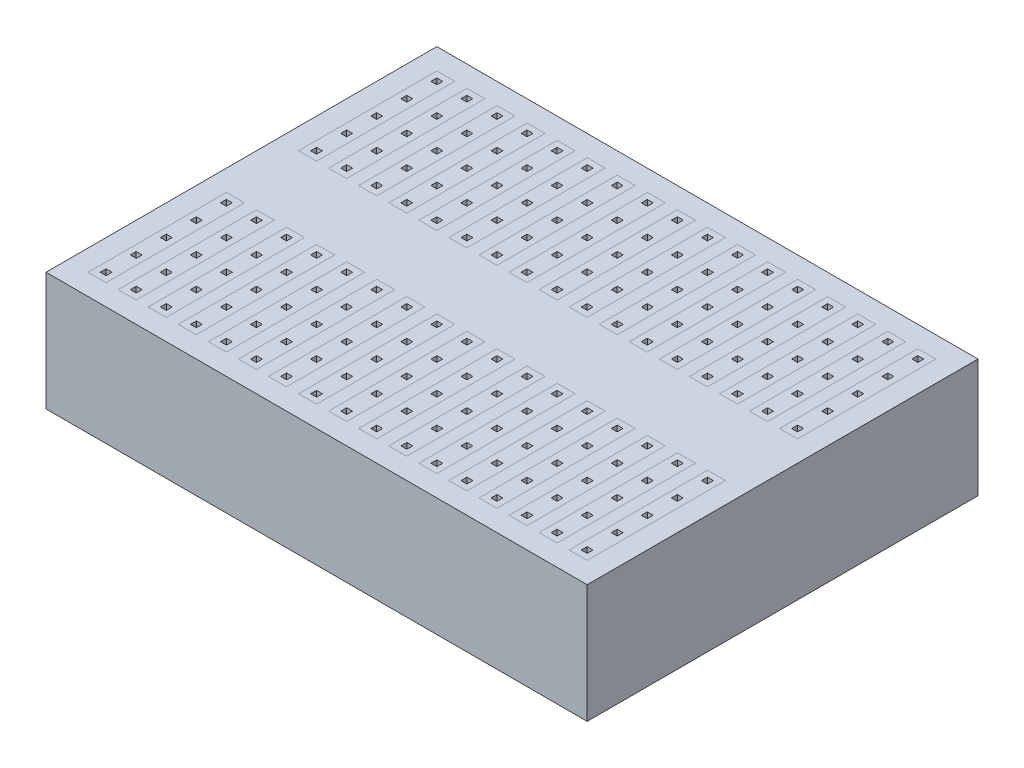
SolidWorks part; units mm, degrees
ref_plane "Front Plane" through (0, 0, 0) normal (0, 0, 1) x (1, 0, 0)
ref_plane "Top Plane" through (0, 0, 0) normal (0, 1, 0) x (1, 0, 0)
ref_plane "Right Plane" through (0, 0, 0) normal (1, 0, 0) x (0, 0, -1)
sketch "Sketch: Protoboard Body" plane through (0, 0, 0) normal (0, 1, 0) x (1, 0, 0)
  line L1 (-22.86, -16.51) -> (22.86, -16.51)
  line L2 (-22.86, -16.51) -> (-22.86, 16.51)
  line L3 (-22.86, 16.51) -> (22.86, 16.51)
  line L4 (22.86, -16.51) -> (22.86, 16.51)
  line L5 (-22.86, -16.51) -> (22.86, 16.51) construction
  line L6 (-22.86, 16.51) -> (22.86, -16.51) construction
  point P0 (0, 0)
extrude "Protoboard Body" add sketch "Sketch: Protoboard Body" against normal blind 10
sketch "Sketch: Terminal Strips" plane through (0, 0, 0) normal (0, 1, 0) x (1, 0, 0)
  line L0 (-18.54, -14.73) -> (-17.02, -14.73)
  line L1 (-21.08, -14.73) -> (-19.56, -14.73)
  line L2 (-21.08, -14.73) -> (-21.08, -3.05)
  line L3 (-21.08, -3.05) -> (-19.56, -3.05)
  line L4 (-19.56, -14.73) -> (-19.56, -3.05)
  line L9 (-18.54, -14.73) -> (-18.54, -3.05)
  line L10 (-18.54, -3.05) -> (-17.02, -3.05)
  line L11 (-17.02, -14.73) -> (-17.02, -3.05)
  line L12 (-16, -14.73) -> (-14.48, -14.73)
  line L13 (-16, -14.73) -> (-16, -3.05)
  line L14 (-16, -3.05) -> (-14.48, -3.05)
  line L15 (-14.48, -14.73) -> (-14.48, -3.05)
  line L16 (-13.46, -14.73) -> (-11.94, -14.73)
  line L17 (-13.46, -14.73) -> (-13.46, -3.05)
  line L18 (-13.46, -3.05) -> (-11.94, -3.05)
  line L19 (-11.94, -14.73) -> (-11.94, -3.05)
  line L20 (-10.92, -14.73) -> (-9.4, -14.73)
  line L21 (-10.92, -14.73) -> (-10.92, -3.05)
  line L22 (-10.92, -3.05) -> (-9.4, -3.05)
  line L23 (-9.4, -14.73) -> (-9.4, -3.05)
  line L24 (-8.38, -14.73) -> (-6.86, -14.73)
  line L25 (-8.38, -14.73) -> (-8.38, -3.05)
  line L26 (-8.38, -3.05) -> (-6.86, -3.05)
  line L27 (-6.86, -14.73) -> (-6.86, -3.05)
  line L28 (-5.84, -14.73) -> (-4.32, -14.73)
  line L29 (-5.84, -14.73) -> (-5.84, -3.05)
  line L30 (-5.84, -3.05) -> (-4.32, -3.05)
  line L31 (-4.32, -14.73) -> (-4.32, -3.05)
  line L32 (-3.3, -14.73) -> (-1.78, -14.73)
  line L33 (-3.3, -14.73) -> (-3.3, -3.05)
  line L34 (-3.3, -3.05) -> (-1.78, -3.05)
  line L35 (-1.78, -14.73) -> (-1.78, -3.05)
  line L36 (-0.76, -14.73) -> (0.76, -14.73)
  line L37 (-0.76, -14.73) -> (-0.76, -3.05)
  line L38 (-0.76, -3.05) -> (0.76, -3.05)
  line L39 (0.76, -14.73) -> (0.76, -3.05)
  line L40 (1.78, -14.73) -> (3.3, -14.73)
  line L41 (1.78, -14.73) -> (1.78, -3.05)
  line L42 (1.78, -3.05) -> (3.3, -3.05)
  line L43 (3.3, -14.73) -> (3.3, -3.05)
  line L44 (4.32, -14.73) -> (5.84, -14.73)
  line L45 (4.32, -14.73) -> (4.32, -3.05)
  line L46 (4.32, -3.05) -> (5.84, -3.05)
  line L47 (5.84, -14.73) -> (5.84, -3.05)
  line L48 (6.86, -14.73) -> (8.38, -14.73)
  line L49 (6.86, -14.73) -> (6.86, -3.05)
  line L50 (6.86, -3.05) -> (8.38, -3.05)
  line L51 (8.38, -14.73) -> (8.38, -3.05)
  line L52 (9.4, -14.73) -> (10.92, -14.73)
  line L53 (9.4, -14.73) -> (9.4, -3.05)
  line L54 (9.4, -3.05) -> (10.92, -3.05)
  line L55 (10.92, -14.73) -> (10.92, -3.05)
  line L56 (11.94, -14.73) -> (13.46, -14.73)
  line L57 (11.94, -14.73) -> (11.94, -3.05)
  line L58 (11.94, -3.05) -> (13.46, -3.05)
  line L59 (13.46, -14.73) -> (13.46, -3.05)
  line L60 (14.48, -14.73) -> (16, -14.73)
  line L61 (14.48, -14.73) -> (14.48, -3.05)
  line L62 (14.48, -3.05) -> (16, -3.05)
  line L63 (16, -14.73) -> (16, -3.05)
  line L64 (17.02, -14.73) -> (18.54, -14.73)
  line L65 (17.02, -14.73) -> (17.02, -3.05)
  line L66 (17.02, -3.05) -> (18.54, -3.05)
  line L67 (18.54, -14.73) -> (18.54, -3.05)
  line L68 (19.56, -14.73) -> (21.08, -14.73)
  line L69 (19.56, -14.73) -> (19.56, -3.05)
  line L70 (19.56, -3.05) -> (21.08, -3.05)
  line L71 (21.08, -14.73) -> (21.08, -3.05)
  line L72 (-18.54, 3.05) -> (-17.02, 3.05)
  line L73 (-18.54, 3.05) -> (-18.54, 14.73)
  line L74 (-18.54, 14.73) -> (-17.02, 14.73)
  line L75 (-17.02, 3.05) -> (-17.02, 14.73)
  line L76 (-16, 3.05) -> (-14.48, 3.05)
  line L77 (-16, 3.05) -> (-16, 14.73)
  line L78 (-16, 14.73) -> (-14.48, 14.73)
  line L79 (-14.48, 3.05) -> (-14.48, 14.73)
  line L80 (-13.46, 3.05) -> (-11.94, 3.05)
  line L81 (-13.46, 3.05) -> (-13.46, 14.73)
  line L82 (-13.46, 14.73) -> (-11.94, 14.73)
  line L83 (-11.94, 3.05) -> (-11.94, 14.73)
  line L84 (-10.92, 3.05) -> (-9.4, 3.05)
  line L85 (-10.92, 3.05) -> (-10.92, 14.73)
  line L86 (-10.92, 14.73) -> (-9.4, 14.73)
  line L87 (-9.4, 3.05) -> (-9.4, 14.73)
  line L88 (-8.38, 3.05) -> (-6.86, 3.05)
  line L89 (-8.38, 3.05) -> (-8.38, 14.73)
  line L90 (-8.38, 14.73) -> (-6.86, 14.73)
  line L91 (-6.86, 3.05) -> (-6.86, 14.73)
  line L92 (-5.84, 3.05) -> (-4.32, 3.05)
  line L93 (-5.84, 3.05) -> (-5.84, 14.73)
  line L94 (-5.84, 14.73) -> (-4.32, 14.73)
  line L95 (-4.32, 3.05) -> (-4.32, 14.73)
  line L96 (-3.3, 3.05) -> (-1.78, 3.05)
  line L97 (-3.3, 3.05) -> (-3.3, 14.73)
  line L98 (-3.3, 14.73) -> (-1.78, 14.73)
  line L99 (-1.78, 3.05) -> (-1.78, 14.73)
  line L100 (-0.76, 3.05) -> (0.76, 3.05)
  line L101 (-0.76, 3.05) -> (-0.76, 14.73)
  line L102 (-0.76, 14.73) -> (0.76, 14.73)
  line L103 (0.76, 3.05) -> (0.76, 14.73)
  line L104 (1.78, 3.05) -> (3.3, 3.05)
  line L105 (1.78, 3.05) -> (1.78, 14.73)
  line L106 (1.78, 14.73) -> (3.3, 14.73)
  line L107 (3.3, 3.05) -> (3.3, 14.73)
  line L108 (4.32, 3.05) -> (5.84, 3.05)
  line L109 (4.32, 3.05) -> (4.32, 14.73)
  line L110 (4.32, 14.73) -> (5.84, 14.73)
  line L111 (5.84, 3.05) -> (5.84, 14.73)
  line L112 (6.86, 3.05) -> (8.38, 3.05)
  line L113 (6.86, 3.05) -> (6.86, 14.73)
  line L114 (6.86, 14.73) -> (8.38, 14.73)
  line L115 (8.38, 3.05) -> (8.38, 14.73)
  line L116 (9.4, 3.05) -> (10.92, 3.05)
  line L117 (9.4, 3.05) -> (9.4, 14.73)
  line L118 (9.4, 14.73) -> (10.92, 14.73)
  line L119 (10.92, 3.05) -> (10.92, 14.73)
  line L120 (11.94, 3.05) -> (13.46, 3.05)
  line L121 (11.94, 3.05) -> (11.94, 14.73)
  line L122 (11.94, 14.73) -> (13.46, 14.73)
  line L123 (13.46, 3.05) -> (13.46, 14.73)
  line L124 (14.48, 3.05) -> (16, 3.05)
  line L125 (14.48, 3.05) -> (14.48, 14.73)
  line L126 (14.48, 14.73) -> (16, 14.73)
  line L127 (16, 3.05) -> (16, 14.73)
  line L128 (17.02, 3.05) -> (18.54, 3.05)
  line L129 (17.02, 3.05) -> (17.02, 14.73)
  line L130 (17.02, 14.73) -> (18.54, 14.73)
  line L131 (18.54, 3.05) -> (18.54, 14.73)
  line L132 (19.56, 3.05) -> (21.08, 3.05)
  line L133 (19.56, 3.05) -> (19.56, 14.73)
  line L134 (19.56, 14.73) -> (21.08, 14.73)
  line L135 (21.08, 3.05) -> (21.08, 14.73)
  line L136 (-21.08, 3.05) -> (-19.56, 3.05)
  line L137 (-21.08, 3.05) -> (-21.08, 14.73)
  line L138 (-21.08, 14.73) -> (-19.56, 14.73)
  line L139 (-19.56, 3.05) -> (-19.56, 14.73)
extrude "Space for Terminal Strips" cut sketch "Sketch: Terminal Strips" against normal blind 8.4
extrude "Terminal Strips" add sketch "Sketch3<2>" against normal blind 8.4 separate body
sketch "Sketch3<2>" plane through (0, 0, 0) normal (0, 1, 0) x (1, 0, 0) same geometry as "Sketch: Terminal Strips"
sketch "Sketch: Pin Holes" plane through (0, 0, 0) normal (0, 1, 0) x (1, 0, 0)
  line L1 (-20.57, -14.22) -> (-20.07, -14.22)
  line L2 (-20.57, -14.22) -> (-20.57, -13.72)
  line L3 (-20.57, -13.72) -> (-20.07, -13.72)
  line L4 (-20.07, -14.22) -> (-20.07, -13.72)
  line L5 (-20.57, -14.22) -> (-20.07, -13.72) construction
  line L6 (-20.57, -13.72) -> (-20.07, -14.22) construction
  line L8 (-20.57, -11.68) -> (-20.07, -11.68)
  line L9 (-20.57, -11.68) -> (-20.57, -11.18)
  line L10 (-20.57, -11.18) -> (-20.07, -11.18)
  line L11 (-20.07, -11.68) -> (-20.07, -11.18)
  line L12 (-20.57, -11.68) -> (-20.07, -11.18) construction
  line L13 (-20.57, -11.18) -> (-20.07, -11.68) construction
  line L14 (-20.57, -9.14) -> (-20.07, -9.14)
  line L15 (-20.57, -9.14) -> (-20.57, -8.64)
  line L16 (-20.57, -8.64) -> (-20.07, -8.64)
  line L17 (-20.07, -9.14) -> (-20.07, -8.64)
  line L18 (-20.57, -9.14) -> (-20.07, -8.64) construction
  line L19 (-20.57, -8.64) -> (-20.07, -9.14) construction
  line L20 (-20.57, -6.6) -> (-20.07, -6.6)
  line L21 (-20.57, -6.6) -> (-20.57, -6.1)
  line L22 (-20.57, -6.1) -> (-20.07, -6.1)
  line L23 (-20.07, -6.6) -> (-20.07, -6.1)
  line L24 (-20.57, -6.6) -> (-20.07, -6.1) construction
  line L25 (-20.57, -6.1) -> (-20.07, -6.6) construction
  line L26 (-20.57, -4.06) -> (-20.07, -4.06)
  line L27 (-20.57, -4.06) -> (-20.57, -3.56)
  line L28 (-20.57, -3.56) -> (-20.07, -3.56)
  line L29 (-20.07, -4.06) -> (-20.07, -3.56)
  line L30 (-20.57, -4.06) -> (-20.07, -3.56) construction
  line L31 (-20.57, -3.56) -> (-20.07, -4.06) construction
  line L32 (-20.57, -1.52) -> (-20.07, -1.52) [skipped]
  line L33 (-20.57, -1.52) -> (-20.57, -1.02) [skipped]
  line L34 (-20.57, -1.02) -> (-20.07, -1.02) [skipped]
  line L35 (-20.07, -1.52) -> (-20.07, -1.02) [skipped]
  line L36 (-20.57, -1.52) -> (-20.07, -1.02) construction
  line L37 (-20.57, -1.02) -> (-20.07, -1.52) construction
  line L38 (-20.57, 1.02) -> (-20.07, 1.02) [skipped]
  line L39 (-20.57, 1.02) -> (-20.57, 1.52) [skipped]
  line L40 (-20.57, 1.52) -> (-20.07, 1.52) [skipped]
  line L41 (-20.07, 1.02) -> (-20.07, 1.52) [skipped]
  line L42 (-20.57, 1.02) -> (-20.07, 1.52) construction
  line L43 (-20.57, 1.52) -> (-20.07, 1.02) construction
  line L44 (-20.57, 3.56) -> (-20.07, 3.56)
  line L45 (-20.57, 3.56) -> (-20.57, 4.06)
  line L46 (-20.57, 4.06) -> (-20.07, 4.06)
  line L47 (-20.07, 3.56) -> (-20.07, 4.06)
  line L48 (-20.57, 3.56) -> (-20.07, 4.06) construction
  line L49 (-20.57, 4.06) -> (-20.07, 3.56) construction
  line L50 (-20.57, 6.1) -> (-20.07, 6.1)
  line L51 (-20.57, 6.1) -> (-20.57, 6.6)
  line L52 (-20.57, 6.6) -> (-20.07, 6.6)
  line L53 (-20.07, 6.1) -> (-20.07, 6.6)
  line L54 (-20.57, 6.1) -> (-20.07, 6.6) construction
  line L55 (-20.57, 6.6) -> (-20.07, 6.1) construction
  line L56 (-20.57, 8.64) -> (-20.07, 8.64)
  line L57 (-20.57, 8.64) -> (-20.57, 9.14)
  line L58 (-20.57, 9.14) -> (-20.07, 9.14)
  line L59 (-20.07, 8.64) -> (-20.07, 9.14)
  line L60 (-20.57, 8.64) -> (-20.07, 9.14) construction
  line L61 (-20.57, 9.14) -> (-20.07, 8.64) construction
  line L62 (-20.57, 11.18) -> (-20.07, 11.18)
  line L63 (-20.57, 11.18) -> (-20.57, 11.68)
  line L64 (-20.57, 11.68) -> (-20.07, 11.68)
  line L65 (-20.07, 11.18) -> (-20.07, 11.68)
  line L66 (-20.57, 11.18) -> (-20.07, 11.68) construction
  line L67 (-20.57, 11.68) -> (-20.07, 11.18) construction
  line L68 (-20.57, 13.72) -> (-20.07, 13.72)
  line L69 (-20.57, 13.72) -> (-20.57, 14.22)
  line L70 (-20.57, 14.22) -> (-20.07, 14.22)
  line L71 (-20.07, 13.72) -> (-20.07, 14.22)
  line L72 (-20.57, 13.72) -> (-20.07, 14.22) construction
  line L73 (-20.57, 14.22) -> (-20.07, 13.72) construction
  line L74 (-18.03, -14.22) -> (-17.53, -14.22)
  line L75 (-18.03, -14.22) -> (-18.03, -13.72)
  line L76 (-18.03, -13.72) -> (-17.53, -13.72)
  line L77 (-17.53, -14.22) -> (-17.53, -13.72)
  line L78 (-18.03, -11.68) -> (-17.53, -11.68)
  line L79 (-18.03, -11.68) -> (-18.03, -11.18)
  line L80 (-18.03, -11.18) -> (-17.53, -11.18)
  line L81 (-17.53, -11.68) -> (-17.53, -11.18)
  line L82 (-18.03, -9.14) -> (-17.53, -9.14)
  line L83 (-18.03, -9.14) -> (-18.03, -8.64)
  line L84 (-18.03, -8.64) -> (-17.53, -8.64)
  line L85 (-17.53, -9.14) -> (-17.53, -8.64)
  line L86 (-18.03, -6.6) -> (-17.53, -6.6)
  line L87 (-18.03, -6.6) -> (-18.03, -6.1)
  line L88 (-18.03, -6.1) -> (-17.53, -6.1)
  line L89 (-17.53, -6.6) -> (-17.53, -6.1)
  line L90 (-18.03, -4.06) -> (-17.53, -4.06)
  line L91 (-18.03, -4.06) -> (-18.03, -3.56)
  line L92 (-18.03, -3.56) -> (-17.53, -3.56)
  line L93 (-17.53, -4.06) -> (-17.53, -3.56)
  line L94 (-18.03, 3.56) -> (-17.53, 3.56)
  line L95 (-18.03, 3.56) -> (-18.03, 4.06)
  line L96 (-18.03, 4.06) -> (-17.53, 4.06)
  line L97 (-17.53, 3.56) -> (-17.53, 4.06)
  line L98 (-18.03, 6.1) -> (-17.53, 6.1)
  line L99 (-18.03, 6.1) -> (-18.03, 6.6)
  line L100 (-18.03, 6.6) -> (-17.53, 6.6)
  line L101 (-17.53, 6.1) -> (-17.53, 6.6)
  line L102 (-18.03, 8.64) -> (-17.53, 8.64)
  line L103 (-18.03, 8.64) -> (-18.03, 9.14)
  line L104 (-18.03, 9.14) -> (-17.53, 9.14)
  line L105 (-17.53, 8.64) -> (-17.53, 9.14)
  line L106 (-18.03, 11.18) -> (-17.53, 11.18)
  line L107 (-18.03, 11.18) -> (-18.03, 11.68)
  line L108 (-18.03, 11.68) -> (-17.53, 11.68)
  line L109 (-17.53, 11.18) -> (-17.53, 11.68)
  line L110 (-18.03, 13.72) -> (-17.53, 13.72)
  line L111 (-18.03, 13.72) -> (-18.03, 14.22)
  line L112 (-18.03, 14.22) -> (-17.53, 14.22)
  line L113 (-17.53, 13.72) -> (-17.53, 14.22)
  line L114 (-18.03, -14.22) -> (-17.53, -13.72) construction
  line L115 (-18.03, -13.72) -> (-17.53, -14.22) construction
  line L116 (-18.03, -11.68) -> (-17.53, -11.18) construction
  line L117 (-18.03, -11.18) -> (-17.53, -11.68) construction
  line L118 (-18.03, -9.14) -> (-17.53, -8.64) construction
  line L119 (-18.03, -8.64) -> (-17.53, -9.14) construction
  line L120 (-18.03, -6.6) -> (-17.53, -6.1) construction
  line L121 (-18.03, -6.1) -> (-17.53, -6.6) construction
  line L122 (-18.03, -4.06) -> (-17.53, -3.56) construction
  line L123 (-18.03, -3.56) -> (-17.53, -4.06) construction
  line L124 (-18.03, 3.56) -> (-17.53, 4.06) construction
  line L125 (-18.03, 4.06) -> (-17.53, 3.56) construction
  line L126 (-18.03, 6.1) -> (-17.53, 6.6) construction
  line L127 (-18.03, 6.6) -> (-17.53, 6.1) construction
  line L128 (-18.03, 8.64) -> (-17.53, 9.14) construction
  line L129 (-18.03, 9.14) -> (-17.53, 8.64) construction
  line L130 (-18.03, 11.18) -> (-17.53, 11.68) construction
  line L131 (-18.03, 11.68) -> (-17.53, 11.18) construction
  line L132 (-18.03, 13.72) -> (-17.53, 14.22) construction
  line L133 (-18.03, 14.22) -> (-17.53, 13.72) construction
  line L134 (-15.49, -14.22) -> (-14.99, -14.22)
  line L135 (-15.49, -14.22) -> (-15.49, -13.72)
  line L136 (-15.49, -13.72) -> (-14.99, -13.72)
  line L137 (-14.99, -14.22) -> (-14.99, -13.72)
  line L138 (-15.49, -11.68) -> (-14.99, -11.68)
  line L139 (-15.49, -11.68) -> (-15.49, -11.18)
  line L140 (-15.49, -11.18) -> (-14.99, -11.18)
  line L141 (-14.99, -11.68) -> (-14.99, -11.18)
  line L142 (-15.49, -9.14) -> (-14.99, -9.14)
  line L143 (-15.49, -9.14) -> (-15.49, -8.64)
  line L144 (-15.49, -8.64) -> (-14.99, -8.64)
  line L145 (-14.99, -9.14) -> (-14.99, -8.64)
  line L146 (-15.49, -6.6) -> (-14.99, -6.6)
  line L147 (-15.49, -6.6) -> (-15.49, -6.1)
  line L148 (-15.49, -6.1) -> (-14.99, -6.1)
  line L149 (-14.99, -6.6) -> (-14.99, -6.1)
  line L150 (-15.49, -4.06) -> (-14.99, -4.06)
  line L151 (-15.49, -4.06) -> (-15.49, -3.56)
  line L152 (-15.49, -3.56) -> (-14.99, -3.56)
  line L153 (-14.99, -4.06) -> (-14.99, -3.56)
  line L154 (-15.49, 3.56) -> (-14.99, 3.56)
  line L155 (-15.49, 3.56) -> (-15.49, 4.06)
  line L156 (-15.49, 4.06) -> (-14.99, 4.06)
  line L157 (-14.99, 3.56) -> (-14.99, 4.06)
  line L158 (-15.49, 6.1) -> (-14.99, 6.1)
  line L159 (-15.49, 6.1) -> (-15.49, 6.6)
  line L160 (-15.49, 6.6) -> (-14.99, 6.6)
  line L161 (-14.99, 6.1) -> (-14.99, 6.6)
  line L162 (-15.49, 8.64) -> (-14.99, 8.64)
  line L163 (-15.49, 8.64) -> (-15.49, 9.14)
  line L164 (-15.49, 9.14) -> (-14.99, 9.14)
  line L165 (-14.99, 8.64) -> (-14.99, 9.14)
  line L166 (-15.49, 11.18) -> (-14.99, 11.18)
  line L167 (-15.49, 11.18) -> (-15.49, 11.68)
  line L168 (-15.49, 11.68) -> (-14.99, 11.68)
  line L169 (-14.99, 11.18) -> (-14.99, 11.68)
  line L170 (-15.49, 13.72) -> (-14.99, 13.72)
  line L171 (-15.49, 13.72) -> (-15.49, 14.22)
  line L172 (-15.49, 14.22) -> (-14.99, 14.22)
  line L173 (-14.99, 13.72) -> (-14.99, 14.22)
  line L174 (-15.49, -14.22) -> (-14.99, -13.72) construction
  line L175 (-15.49, -13.72) -> (-14.99, -14.22) construction
  line L176 (-15.49, -11.68) -> (-14.99, -11.18) construction
  line L177 (-15.49, -11.18) -> (-14.99, -11.68) construction
  line L178 (-15.49, -9.14) -> (-14.99, -8.64) construction
  line L179 (-15.49, -8.64) -> (-14.99, -9.14) construction
  line L180 (-15.49, -6.6) -> (-14.99, -6.1) construction
  line L181 (-15.49, -6.1) -> (-14.99, -6.6) construction
  line L182 (-15.49, -4.06) -> (-14.99, -3.56) construction
  line L183 (-15.49, -3.56) -> (-14.99, -4.06) construction
  line L184 (-15.49, 3.56) -> (-14.99, 4.06) construction
  line L185 (-15.49, 4.06) -> (-14.99, 3.56) construction
  line L186 (-15.49, 6.1) -> (-14.99, 6.6) construction
  line L187 (-15.49, 6.6) -> (-14.99, 6.1) construction
  line L188 (-15.49, 8.64) -> (-14.99, 9.14) construction
  line L189 (-15.49, 9.14) -> (-14.99, 8.64) construction
  line L190 (-15.49, 11.18) -> (-14.99, 11.68) construction
  line L191 (-15.49, 11.68) -> (-14.99, 11.18) construction
  line L192 (-15.49, 13.72) -> (-14.99, 14.22) construction
  line L193 (-15.49, 14.22) -> (-14.99, 13.72) construction
  line L194 (-12.95, -14.22) -> (-12.45, -14.22)
  line L195 (-12.95, -14.22) -> (-12.95, -13.72)
  line L196 (-12.95, -13.72) -> (-12.45, -13.72)
  line L197 (-12.45, -14.22) -> (-12.45, -13.72)
  line L198 (-12.95, -11.68) -> (-12.45, -11.68)
  line L199 (-12.95, -11.68) -> (-12.95, -11.18)
  line L200 (-12.95, -11.18) -> (-12.45, -11.18)
  line L201 (-12.45, -11.68) -> (-12.45, -11.18)
  line L202 (-12.95, -9.14) -> (-12.45, -9.14)
  line L203 (-12.95, -9.14) -> (-12.95, -8.64)
  line L204 (-12.95, -8.64) -> (-12.45, -8.64)
  line L205 (-12.45, -9.14) -> (-12.45, -8.64)
  line L206 (-12.95, -6.6) -> (-12.45, -6.6)
  line L207 (-12.95, -6.6) -> (-12.95, -6.1)
  line L208 (-12.95, -6.1) -> (-12.45, -6.1)
  line L209 (-12.45, -6.6) -> (-12.45, -6.1)
  line L210 (-12.95, -4.06) -> (-12.45, -4.06)
  line L211 (-12.95, -4.06) -> (-12.95, -3.56)
  line L212 (-12.95, -3.56) -> (-12.45, -3.56)
  line L213 (-12.45, -4.06) -> (-12.45, -3.56)
  line L214 (-12.95, 3.56) -> (-12.45, 3.56)
  line L215 (-12.95, 3.56) -> (-12.95, 4.06)
  line L216 (-12.95, 4.06) -> (-12.45, 4.06)
  line L217 (-12.45, 3.56) -> (-12.45, 4.06)
  line L218 (-12.95, 6.1) -> (-12.45, 6.1)
  line L219 (-12.95, 6.1) -> (-12.95, 6.6)
  line L220 (-12.95, 6.6) -> (-12.45, 6.6)
  line L221 (-12.45, 6.1) -> (-12.45, 6.6)
  line L222 (-12.95, 8.64) -> (-12.45, 8.64)
  line L223 (-12.95, 8.64) -> (-12.95, 9.14)
  line L224 (-12.95, 9.14) -> (-12.45, 9.14)
  line L225 (-12.45, 8.64) -> (-12.45, 9.14)
  line L226 (-12.95, 11.18) -> (-12.45, 11.18)
  line L227 (-12.95, 11.18) -> (-12.95, 11.68)
  line L228 (-12.95, 11.68) -> (-12.45, 11.68)
  line L229 (-12.45, 11.18) -> (-12.45, 11.68)
  line L230 (-12.95, 13.72) -> (-12.45, 13.72)
  line L231 (-12.95, 13.72) -> (-12.95, 14.22)
  line L232 (-12.95, 14.22) -> (-12.45, 14.22)
  line L233 (-12.45, 13.72) -> (-12.45, 14.22)
  line L234 (-12.95, -14.22) -> (-12.45, -13.72) construction
  line L235 (-12.95, -13.72) -> (-12.45, -14.22) construction
  line L236 (-12.95, -11.68) -> (-12.45, -11.18) construction
  line L237 (-12.95, -11.18) -> (-12.45, -11.68) construction
  line L238 (-12.95, -9.14) -> (-12.45, -8.64) construction
  line L239 (-12.95, -8.64) -> (-12.45, -9.14) construction
  line L240 (-12.95, -6.6) -> (-12.45, -6.1) construction
  line L241 (-12.95, -6.1) -> (-12.45, -6.6) construction
  line L242 (-12.95, -4.06) -> (-12.45, -3.56) construction
  line L243 (-12.95, -3.56) -> (-12.45, -4.06) construction
  line L244 (-12.95, 3.56) -> (-12.45, 4.06) construction
  line L245 (-12.95, 4.06) -> (-12.45, 3.56) construction
  line L246 (-12.95, 6.1) -> (-12.45, 6.6) construction
  line L247 (-12.95, 6.6) -> (-12.45, 6.1) construction
  line L248 (-12.95, 8.64) -> (-12.45, 9.14) construction
  line L249 (-12.95, 9.14) -> (-12.45, 8.64) construction
  line L250 (-12.95, 11.18) -> (-12.45, 11.68) construction
  line L251 (-12.95, 11.68) -> (-12.45, 11.18) construction
  line L252 (-12.95, 13.72) -> (-12.45, 14.22) construction
  line L253 (-12.95, 14.22) -> (-12.45, 13.72) construction
  line L254 (-10.41, -14.22) -> (-9.91, -14.22)
  line L255 (-10.41, -14.22) -> (-10.41, -13.72)
  line L256 (-10.41, -13.72) -> (-9.91, -13.72)
  line L257 (-9.91, -14.22) -> (-9.91, -13.72)
  line L258 (-10.41, -11.68) -> (-9.91, -11.68)
  line L259 (-10.41, -11.68) -> (-10.41, -11.18)
  line L260 (-10.41, -11.18) -> (-9.91, -11.18)
  line L261 (-9.91, -11.68) -> (-9.91, -11.18)
  line L262 (-10.41, -9.14) -> (-9.91, -9.14)
  line L263 (-10.41, -9.14) -> (-10.41, -8.64)
  line L264 (-10.41, -8.64) -> (-9.91, -8.64)
  line L265 (-9.91, -9.14) -> (-9.91, -8.64)
  line L266 (-10.41, -6.6) -> (-9.91, -6.6)
  line L267 (-10.41, -6.6) -> (-10.41, -6.1)
  line L268 (-10.41, -6.1) -> (-9.91, -6.1)
  line L269 (-9.91, -6.6) -> (-9.91, -6.1)
  line L270 (-10.41, -4.06) -> (-9.91, -4.06)
  line L271 (-10.41, -4.06) -> (-10.41, -3.56)
  line L272 (-10.41, -3.56) -> (-9.91, -3.56)
  line L273 (-9.91, -4.06) -> (-9.91, -3.56)
  line L274 (-10.41, 3.56) -> (-9.91, 3.56)
  line L275 (-10.41, 3.56) -> (-10.41, 4.06)
  line L276 (-10.41, 4.06) -> (-9.91, 4.06)
  line L277 (-9.91, 3.56) -> (-9.91, 4.06)
  line L278 (-10.41, 6.1) -> (-9.91, 6.1)
  line L279 (-10.41, 6.1) -> (-10.41, 6.6)
  line L280 (-10.41, 6.6) -> (-9.91, 6.6)
  line L281 (-9.91, 6.1) -> (-9.91, 6.6)
  line L282 (-10.41, 8.64) -> (-9.91, 8.64)
  line L283 (-10.41, 8.64) -> (-10.41, 9.14)
  line L284 (-10.41, 9.14) -> (-9.91, 9.14)
  line L285 (-9.91, 8.64) -> (-9.91, 9.14)
  line L286 (-10.41, 11.18) -> (-9.91, 11.18)
  line L287 (-10.41, 11.18) -> (-10.41, 11.68)
  line L288 (-10.41, 11.68) -> (-9.91, 11.68)
  line L289 (-9.91, 11.18) -> (-9.91, 11.68)
  line L290 (-10.41, 13.72) -> (-9.91, 13.72)
  line L291 (-10.41, 13.72) -> (-10.41, 14.22)
  line L292 (-10.41, 14.22) -> (-9.91, 14.22)
  line L293 (-9.91, 13.72) -> (-9.91, 14.22)
  line L294 (-10.41, -14.22) -> (-9.91, -13.72) construction
  line L295 (-10.41, -13.72) -> (-9.91, -14.22) construction
  line L296 (-10.41, -11.68) -> (-9.91, -11.18) construction
  line L297 (-10.41, -11.18) -> (-9.91, -11.68) construction
  line L298 (-10.41, -9.14) -> (-9.91, -8.64) construction
  line L299 (-10.41, -8.64) -> (-9.91, -9.14) construction
  line L300 (-10.41, -6.6) -> (-9.91, -6.1) construction
  line L301 (-10.41, -6.1) -> (-9.91, -6.6) construction
  line L302 (-10.41, -4.06) -> (-9.91, -3.56) construction
  line L303 (-10.41, -3.56) -> (-9.91, -4.06) construction
  line L304 (-10.41, 3.56) -> (-9.91, 4.06) construction
  line L305 (-10.41, 4.06) -> (-9.91, 3.56) construction
  line L306 (-10.41, 6.1) -> (-9.91, 6.6) construction
  line L307 (-10.41, 6.6) -> (-9.91, 6.1) construction
  line L308 (-10.41, 8.64) -> (-9.91, 9.14) construction
  line L309 (-10.41, 9.14) -> (-9.91, 8.64) construction
  line L310 (-10.41, 11.18) -> (-9.91, 11.68) construction
  line L311 (-10.41, 11.68) -> (-9.91, 11.18) construction
  line L312 (-10.41, 13.72) -> (-9.91, 14.22) construction
  line L313 (-10.41, 14.22) -> (-9.91, 13.72) construction
  line L314 (-7.87, -14.22) -> (-7.37, -14.22)
  line L315 (-7.87, -14.22) -> (-7.87, -13.72)
  line L316 (-7.87, -13.72) -> (-7.37, -13.72)
  line L317 (-7.37, -14.22) -> (-7.37, -13.72)
  line L318 (-7.87, -11.68) -> (-7.37, -11.68)
  line L319 (-7.87, -11.68) -> (-7.87, -11.18)
  line L320 (-7.87, -11.18) -> (-7.37, -11.18)
  line L321 (-7.37, -11.68) -> (-7.37, -11.18)
  line L322 (-7.87, -9.14) -> (-7.37, -9.14)
  line L323 (-7.87, -9.14) -> (-7.87, -8.64)
  line L324 (-7.87, -8.64) -> (-7.37, -8.64)
  line L325 (-7.37, -9.14) -> (-7.37, -8.64)
  line L326 (-7.87, -6.6) -> (-7.37, -6.6)
  line L327 (-7.87, -6.6) -> (-7.87, -6.1)
  line L328 (-7.87, -6.1) -> (-7.37, -6.1)
  line L329 (-7.37, -6.6) -> (-7.37, -6.1)
  line L330 (-7.87, -4.06) -> (-7.37, -4.06)
  line L331 (-7.87, -4.06) -> (-7.87, -3.56)
  line L332 (-7.87, -3.56) -> (-7.37, -3.56)
  line L333 (-7.37, -4.06) -> (-7.37, -3.56)
  line L334 (-7.87, 3.56) -> (-7.37, 3.56)
  line L335 (-7.87, 3.56) -> (-7.87, 4.06)
  line L336 (-7.87, 4.06) -> (-7.37, 4.06)
  line L337 (-7.37, 3.56) -> (-7.37, 4.06)
  line L338 (-7.87, 6.1) -> (-7.37, 6.1)
  line L339 (-7.87, 6.1) -> (-7.87, 6.6)
  line L340 (-7.87, 6.6) -> (-7.37, 6.6)
  line L341 (-7.37, 6.1) -> (-7.37, 6.6)
  line L342 (-7.87, 8.64) -> (-7.37, 8.64)
  line L343 (-7.87, 8.64) -> (-7.87, 9.14)
  line L344 (-7.87, 9.14) -> (-7.37, 9.14)
  line L345 (-7.37, 8.64) -> (-7.37, 9.14)
  line L346 (-7.87, 11.18) -> (-7.37, 11.18)
  line L347 (-7.87, 11.18) -> (-7.87, 11.68)
  line L348 (-7.87, 11.68) -> (-7.37, 11.68)
  line L349 (-7.37, 11.18) -> (-7.37, 11.68)
  line L350 (-7.87, 13.72) -> (-7.37, 13.72)
  line L351 (-7.87, 13.72) -> (-7.87, 14.22)
  line L352 (-7.87, 14.22) -> (-7.37, 14.22)
  line L353 (-7.37, 13.72) -> (-7.37, 14.22)
  line L354 (-7.87, -14.22) -> (-7.37, -13.72) construction
  line L355 (-7.87, -13.72) -> (-7.37, -14.22) construction
  line L356 (-7.87, -11.68) -> (-7.37, -11.18) construction
  line L357 (-7.87, -11.18) -> (-7.37, -11.68) construction
  line L358 (-7.87, -9.14) -> (-7.37, -8.64) construction
  line L359 (-7.87, -8.64) -> (-7.37, -9.14) construction
  line L360 (-7.87, -6.6) -> (-7.37, -6.1) construction
  line L361 (-7.87, -6.1) -> (-7.37, -6.6) construction
  line L362 (-7.87, -4.06) -> (-7.37, -3.56) construction
  line L363 (-7.87, -3.56) -> (-7.37, -4.06) construction
  line L364 (-7.87, 3.56) -> (-7.37, 4.06) construction
  line L365 (-7.87, 4.06) -> (-7.37, 3.56) construction
  line L366 (-7.87, 6.1) -> (-7.37, 6.6) construction
  line L367 (-7.87, 6.6) -> (-7.37, 6.1) construction
  line L368 (-7.87, 8.64) -> (-7.37, 9.14) construction
  line L369 (-7.87, 9.14) -> (-7.37, 8.64) construction
  line L370 (-7.87, 11.18) -> (-7.37, 11.68) construction
  line L371 (-7.87, 11.68) -> (-7.37, 11.18) construction
  line L372 (-7.87, 13.72) -> (-7.37, 14.22) construction
  line L373 (-7.87, 14.22) -> (-7.37, 13.72) construction
  line L374 (-5.33, -14.22) -> (-4.83, -14.22)
  line L375 (-5.33, -14.22) -> (-5.33, -13.72)
  line L376 (-5.33, -13.72) -> (-4.83, -13.72)
  line L377 (-4.83, -14.22) -> (-4.83, -13.72)
  line L378 (-5.33, -11.68) -> (-4.83, -11.68)
  line L379 (-5.33, -11.68) -> (-5.33, -11.18)
  line L380 (-5.33, -11.18) -> (-4.83, -11.18)
  line L381 (-4.83, -11.68) -> (-4.83, -11.18)
  line L382 (-5.33, -9.14) -> (-4.83, -9.14)
  line L383 (-5.33, -9.14) -> (-5.33, -8.64)
  line L384 (-5.33, -8.64) -> (-4.83, -8.64)
  line L385 (-4.83, -9.14) -> (-4.83, -8.64)
  line L386 (-5.33, -6.6) -> (-4.83, -6.6)
  line L387 (-5.33, -6.6) -> (-5.33, -6.1)
  line L388 (-5.33, -6.1) -> (-4.83, -6.1)
  line L389 (-4.83, -6.6) -> (-4.83, -6.1)
  line L390 (-5.33, -4.06) -> (-4.83, -4.06)
  line L391 (-5.33, -4.06) -> (-5.33, -3.56)
  line L392 (-5.33, -3.56) -> (-4.83, -3.56)
  line L393 (-4.83, -4.06) -> (-4.83, -3.56)
  line L394 (-5.33, 3.56) -> (-4.83, 3.56)
  line L395 (-5.33, 3.56) -> (-5.33, 4.06)
  line L396 (-5.33, 4.06) -> (-4.83, 4.06)
  line L397 (-4.83, 3.56) -> (-4.83, 4.06)
  line L398 (-5.33, 6.1) -> (-4.83, 6.1)
  line L399 (-5.33, 6.1) -> (-5.33, 6.6)
  line L400 (-5.33, 6.6) -> (-4.83, 6.6)
  line L401 (-4.83, 6.1) -> (-4.83, 6.6)
  line L402 (-5.33, 8.64) -> (-4.83, 8.64)
  line L403 (-5.33, 8.64) -> (-5.33, 9.14)
  line L404 (-5.33, 9.14) -> (-4.83, 9.14)
  line L405 (-4.83, 8.64) -> (-4.83, 9.14)
  line L406 (-5.33, 11.18) -> (-4.83, 11.18)
  line L407 (-5.33, 11.18) -> (-5.33, 11.68)
  line L408 (-5.33, 11.68) -> (-4.83, 11.68)
  line L409 (-4.83, 11.18) -> (-4.83, 11.68)
  line L410 (-5.33, 13.72) -> (-4.83, 13.72)
  line L411 (-5.33, 13.72) -> (-5.33, 14.22)
  line L412 (-5.33, 14.22) -> (-4.83, 14.22)
  line L413 (-4.83, 13.72) -> (-4.83, 14.22)
  line L414 (-5.33, -14.22) -> (-4.83, -13.72) construction
  line L415 (-5.33, -13.72) -> (-4.83, -14.22) construction
  line L416 (-5.33, -11.68) -> (-4.83, -11.18) construction
  line L417 (-5.33, -11.18) -> (-4.83, -11.68) construction
  line L418 (-5.33, -9.14) -> (-4.83, -8.64) construction
  line L419 (-5.33, -8.64) -> (-4.83, -9.14) construction
  line L420 (-5.33, -6.6) -> (-4.83, -6.1) construction
  line L421 (-5.33, -6.1) -> (-4.83, -6.6) construction
  line L422 (-5.33, -4.06) -> (-4.83, -3.56) construction
  line L423 (-5.33, -3.56) -> (-4.83, -4.06) construction
  line L424 (-5.33, 3.56) -> (-4.83, 4.06) construction
  line L425 (-5.33, 4.06) -> (-4.83, 3.56) construction
  line L426 (-5.33, 6.1) -> (-4.83, 6.6) construction
  line L427 (-5.33, 6.6) -> (-4.83, 6.1) construction
  line L428 (-5.33, 8.64) -> (-4.83, 9.14) construction
  line L429 (-5.33, 9.14) -> (-4.83, 8.64) construction
  line L430 (-5.33, 11.18) -> (-4.83, 11.68) construction
  line L431 (-5.33, 11.68) -> (-4.83, 11.18) construction
  line L432 (-5.33, 13.72) -> (-4.83, 14.22) construction
  line L433 (-5.33, 14.22) -> (-4.83, 13.72) construction
  line L434 (-2.79, -14.22) -> (-2.29, -14.22)
  line L435 (-2.79, -14.22) -> (-2.79, -13.72)
  line L436 (-2.79, -13.72) -> (-2.29, -13.72)
  line L437 (-2.29, -14.22) -> (-2.29, -13.72)
  line L438 (-2.79, -11.68) -> (-2.29, -11.68)
  line L439 (-2.79, -11.68) -> (-2.79, -11.18)
  line L440 (-2.79, -11.18) -> (-2.29, -11.18)
  line L441 (-2.29, -11.68) -> (-2.29, -11.18)
  line L442 (-2.79, -9.14) -> (-2.29, -9.14)
  line L443 (-2.79, -9.14) -> (-2.79, -8.64)
  line L444 (-2.79, -8.64) -> (-2.29, -8.64)
  line L445 (-2.29, -9.14) -> (-2.29, -8.64)
  line L446 (-2.79, -6.6) -> (-2.29, -6.6)
  line L447 (-2.79, -6.6) -> (-2.79, -6.1)
  line L448 (-2.79, -6.1) -> (-2.29, -6.1)
  line L449 (-2.29, -6.6) -> (-2.29, -6.1)
  line L450 (-2.79, -4.06) -> (-2.29, -4.06)
  line L451 (-2.79, -4.06) -> (-2.79, -3.56)
  line L452 (-2.79, -3.56) -> (-2.29, -3.56)
  line L453 (-2.29, -4.06) -> (-2.29, -3.56)
  line L454 (-2.79, 3.56) -> (-2.29, 3.56)
  line L455 (-2.79, 3.56) -> (-2.79, 4.06)
  line L456 (-2.79, 4.06) -> (-2.29, 4.06)
  line L457 (-2.29, 3.56) -> (-2.29, 4.06)
  line L458 (-2.79, 6.1) -> (-2.29, 6.1)
  line L459 (-2.79, 6.1) -> (-2.79, 6.6)
  line L460 (-2.79, 6.6) -> (-2.29, 6.6)
  line L461 (-2.29, 6.1) -> (-2.29, 6.6)
  line L462 (-2.79, 8.64) -> (-2.29, 8.64)
  line L463 (-2.79, 8.64) -> (-2.79, 9.14)
  line L464 (-2.79, 9.14) -> (-2.29, 9.14)
  line L465 (-2.29, 8.64) -> (-2.29, 9.14)
  line L466 (-2.79, 11.18) -> (-2.29, 11.18)
  line L467 (-2.79, 11.18) -> (-2.79, 11.68)
  line L468 (-2.79, 11.68) -> (-2.29, 11.68)
  line L469 (-2.29, 11.18) -> (-2.29, 11.68)
  line L470 (-2.79, 13.72) -> (-2.29, 13.72)
  line L471 (-2.79, 13.72) -> (-2.79, 14.22)
  line L472 (-2.79, 14.22) -> (-2.29, 14.22)
  line L473 (-2.29, 13.72) -> (-2.29, 14.22)
  line L474 (-2.79, -14.22) -> (-2.29, -13.72) construction
  line L475 (-2.79, -13.72) -> (-2.29, -14.22) construction
  line L476 (-2.79, -11.68) -> (-2.29, -11.18) construction
  line L477 (-2.79, -11.18) -> (-2.29, -11.68) construction
  line L478 (-2.79, -9.14) -> (-2.29, -8.64) construction
  line L479 (-2.79, -8.64) -> (-2.29, -9.14) construction
  line L480 (-2.79, -6.6) -> (-2.29, -6.1) construction
  line L481 (-2.79, -6.1) -> (-2.29, -6.6) construction
  line L482 (-2.79, -4.06) -> (-2.29, -3.56) construction
  line L483 (-2.79, -3.56) -> (-2.29, -4.06) construction
  line L484 (-2.79, 3.56) -> (-2.29, 4.06) construction
  line L485 (-2.79, 4.06) -> (-2.29, 3.56) construction
  line L486 (-2.79, 6.1) -> (-2.29, 6.6) construction
  line L487 (-2.79, 6.6) -> (-2.29, 6.1) construction
  line L488 (-2.79, 8.64) -> (-2.29, 9.14) construction
  line L489 (-2.79, 9.14) -> (-2.29, 8.64) construction
  line L490 (-2.79, 11.18) -> (-2.29, 11.68) construction
  line L491 (-2.79, 11.68) -> (-2.29, 11.18) construction
  line L492 (-2.79, 13.72) -> (-2.29, 14.22) construction
  line L493 (-2.79, 14.22) -> (-2.29, 13.72) construction
  line L494 (-0.25, -14.22) -> (0.25, -14.22)
  line L495 (-0.25, -14.22) -> (-0.25, -13.72)
  line L496 (-0.25, -13.72) -> (0.25, -13.72)
  line L497 (0.25, -14.22) -> (0.25, -13.72)
  line L498 (-0.25, -11.68) -> (0.25, -11.68)
  line L499 (-0.25, -11.68) -> (-0.25, -11.18)
  line L500 (-0.25, -11.18) -> (0.25, -11.18)
  line L501 (0.25, -11.68) -> (0.25, -11.18)
  line L502 (-0.25, -9.14) -> (0.25, -9.14)
  line L503 (-0.25, -9.14) -> (-0.25, -8.64)
  line L504 (-0.25, -8.64) -> (0.25, -8.64)
  line L505 (0.25, -9.14) -> (0.25, -8.64)
  line L506 (-0.25, -6.6) -> (0.25, -6.6)
  line L507 (-0.25, -6.6) -> (-0.25, -6.1)
  line L508 (-0.25, -6.1) -> (0.25, -6.1)
  line L509 (0.25, -6.6) -> (0.25, -6.1)
  line L510 (-0.25, -4.06) -> (0.25, -4.06)
  line L511 (-0.25, -4.06) -> (-0.25, -3.56)
  line L512 (-0.25, -3.56) -> (0.25, -3.56)
  line L513 (0.25, -4.06) -> (0.25, -3.56)
  line L514 (-0.25, 3.56) -> (0.25, 3.56)
  line L515 (-0.25, 3.56) -> (-0.25, 4.06)
  line L516 (-0.25, 4.06) -> (0.25, 4.06)
  line L517 (0.25, 3.56) -> (0.25, 4.06)
  line L518 (-0.25, 6.1) -> (0.25, 6.1)
  line L519 (-0.25, 6.1) -> (-0.25, 6.6)
  line L520 (-0.25, 6.6) -> (0.25, 6.6)
  line L521 (0.25, 6.1) -> (0.25, 6.6)
  line L522 (-0.25, 8.64) -> (0.25, 8.64)
  line L523 (-0.25, 8.64) -> (-0.25, 9.14)
  line L524 (-0.25, 9.14) -> (0.25, 9.14)
  line L525 (0.25, 8.64) -> (0.25, 9.14)
  line L526 (-0.25, 11.18) -> (0.25, 11.18)
  line L527 (-0.25, 11.18) -> (-0.25, 11.68)
  line L528 (-0.25, 11.68) -> (0.25, 11.68)
  line L529 (0.25, 11.18) -> (0.25, 11.68)
  line L530 (-0.25, 13.72) -> (0.25, 13.72)
  line L531 (-0.25, 13.72) -> (-0.25, 14.22)
  line L532 (-0.25, 14.22) -> (0.25, 14.22)
  line L533 (0.25, 13.72) -> (0.25, 14.22)
  line L534 (-0.25, -14.22) -> (0.25, -13.72) construction
  line L535 (-0.25, -13.72) -> (0.25, -14.22) construction
  line L536 (-0.25, -11.68) -> (0.25, -11.18) construction
  line L537 (-0.25, -11.18) -> (0.25, -11.68) construction
  line L538 (-0.25, -9.14) -> (0.25, -8.64) construction
  line L539 (-0.25, -8.64) -> (0.25, -9.14) construction
  line L540 (-0.25, -6.6) -> (0.25, -6.1) construction
  line L541 (-0.25, -6.1) -> (0.25, -6.6) construction
  line L542 (-0.25, -4.06) -> (0.25, -3.56) construction
  line L543 (-0.25, -3.56) -> (0.25, -4.06) construction
  line L544 (-0.25, 3.56) -> (0.25, 4.06) construction
  line L545 (-0.25, 4.06) -> (0.25, 3.56) construction
  line L546 (-0.25, 6.1) -> (0.25, 6.6) construction
  line L547 (-0.25, 6.6) -> (0.25, 6.1) construction
  line L548 (-0.25, 8.64) -> (0.25, 9.14) construction
  line L549 (-0.25, 9.14) -> (0.25, 8.64) construction
  line L550 (-0.25, 11.18) -> (0.25, 11.68) construction
  line L551 (-0.25, 11.68) -> (0.25, 11.18) construction
  line L552 (-0.25, 13.72) -> (0.25, 14.22) construction
  line L553 (-0.25, 14.22) -> (0.25, 13.72) construction
  line L554 (2.29, -14.22) -> (2.79, -14.22)
  line L555 (2.29, -14.22) -> (2.29, -13.72)
  line L556 (2.29, -13.72) -> (2.79, -13.72)
  line L557 (2.79, -14.22) -> (2.79, -13.72)
  line L558 (2.29, -11.68) -> (2.79, -11.68)
  line L559 (2.29, -11.68) -> (2.29, -11.18)
  line L560 (2.29, -11.18) -> (2.79, -11.18)
  line L561 (2.79, -11.68) -> (2.79, -11.18)
  line L562 (2.29, -9.14) -> (2.79, -9.14)
  line L563 (2.29, -9.14) -> (2.29, -8.64)
  line L564 (2.29, -8.64) -> (2.79, -8.64)
  line L565 (2.79, -9.14) -> (2.79, -8.64)
  line L566 (2.29, -6.6) -> (2.79, -6.6)
  line L567 (2.29, -6.6) -> (2.29, -6.1)
  line L568 (2.29, -6.1) -> (2.79, -6.1)
  line L569 (2.79, -6.6) -> (2.79, -6.1)
  line L570 (2.29, -4.06) -> (2.79, -4.06)
  line L571 (2.29, -4.06) -> (2.29, -3.56)
  line L572 (2.29, -3.56) -> (2.79, -3.56)
  line L573 (2.79, -4.06) -> (2.79, -3.56)
  line L574 (2.29, 3.56) -> (2.79, 3.56)
  line L575 (2.29, 3.56) -> (2.29, 4.06)
  line L576 (2.29, 4.06) -> (2.79, 4.06)
  line L577 (2.79, 3.56) -> (2.79, 4.06)
  line L578 (2.29, 6.1) -> (2.79, 6.1)
  line L579 (2.29, 6.1) -> (2.29, 6.6)
  line L580 (2.29, 6.6) -> (2.79, 6.6)
  line L581 (2.79, 6.1) -> (2.79, 6.6)
  line L582 (2.29, 8.64) -> (2.79, 8.64)
  line L583 (2.29, 8.64) -> (2.29, 9.14)
  line L584 (2.29, 9.14) -> (2.79, 9.14)
  line L585 (2.79, 8.64) -> (2.79, 9.14)
  line L586 (2.29, 11.18) -> (2.79, 11.18)
  line L587 (2.29, 11.18) -> (2.29, 11.68)
  line L588 (2.29, 11.68) -> (2.79, 11.68)
  line L589 (2.79, 11.18) -> (2.79, 11.68)
  line L590 (2.29, 13.72) -> (2.79, 13.72)
  line L591 (2.29, 13.72) -> (2.29, 14.22)
  line L592 (2.29, 14.22) -> (2.79, 14.22)
  line L593 (2.79, 13.72) -> (2.79, 14.22)
  line L594 (2.29, -14.22) -> (2.79, -13.72) construction
  line L595 (2.29, -13.72) -> (2.79, -14.22) construction
  line L596 (2.29, -11.68) -> (2.79, -11.18) construction
  line L597 (2.29, -11.18) -> (2.79, -11.68) construction
  line L598 (2.29, -9.14) -> (2.79, -8.64) construction
  line L599 (2.29, -8.64) -> (2.79, -9.14) construction
  line L600 (2.29, -6.6) -> (2.79, -6.1) construction
  line L601 (2.29, -6.1) -> (2.79, -6.6) construction
  line L602 (2.29, -4.06) -> (2.79, -3.56) construction
  line L603 (2.29, -3.56) -> (2.79, -4.06) construction
  line L604 (2.29, 3.56) -> (2.79, 4.06) construction
  line L605 (2.29, 4.06) -> (2.79, 3.56) construction
  line L606 (2.29, 6.1) -> (2.79, 6.6) construction
  line L607 (2.29, 6.6) -> (2.79, 6.1) construction
  line L608 (2.29, 8.64) -> (2.79, 9.14) construction
  line L609 (2.29, 9.14) -> (2.79, 8.64) construction
  line L610 (2.29, 11.18) -> (2.79, 11.68) construction
  line L611 (2.29, 11.68) -> (2.79, 11.18) construction
  line L612 (2.29, 13.72) -> (2.79, 14.22) construction
  line L613 (2.29, 14.22) -> (2.79, 13.72) construction
  line L614 (4.83, -14.22) -> (5.33, -14.22)
  line L615 (4.83, -14.22) -> (4.83, -13.72)
  line L616 (4.83, -13.72) -> (5.33, -13.72)
  line L617 (5.33, -14.22) -> (5.33, -13.72)
  line L618 (4.83, -11.68) -> (5.33, -11.68)
  line L619 (4.83, -11.68) -> (4.83, -11.18)
  line L620 (4.83, -11.18) -> (5.33, -11.18)
  line L621 (5.33, -11.68) -> (5.33, -11.18)
  line L622 (4.83, -9.14) -> (5.33, -9.14)
  line L623 (4.83, -9.14) -> (4.83, -8.64)
  line L624 (4.83, -8.64) -> (5.33, -8.64)
  line L625 (5.33, -9.14) -> (5.33, -8.64)
  line L626 (4.83, -6.6) -> (5.33, -6.6)
  line L627 (4.83, -6.6) -> (4.83, -6.1)
  line L628 (4.83, -6.1) -> (5.33, -6.1)
  line L629 (5.33, -6.6) -> (5.33, -6.1)
  line L630 (4.83, -4.06) -> (5.33, -4.06)
  line L631 (4.83, -4.06) -> (4.83, -3.56)
  line L632 (4.83, -3.56) -> (5.33, -3.56)
  line L633 (5.33, -4.06) -> (5.33, -3.56)
  line L634 (4.83, 3.56) -> (5.33, 3.56)
  line L635 (4.83, 3.56) -> (4.83, 4.06)
  line L636 (4.83, 4.06) -> (5.33, 4.06)
  line L637 (5.33, 3.56) -> (5.33, 4.06)
  line L638 (4.83, 6.1) -> (5.33, 6.1)
  line L639 (4.83, 6.1) -> (4.83, 6.6)
  line L640 (4.83, 6.6) -> (5.33, 6.6)
  line L641 (5.33, 6.1) -> (5.33, 6.6)
  line L642 (4.83, 8.64) -> (5.33, 8.64)
  line L643 (4.83, 8.64) -> (4.83, 9.14)
  line L644 (4.83, 9.14) -> (5.33, 9.14)
  line L645 (5.33, 8.64) -> (5.33, 9.14)
  line L646 (4.83, 11.18) -> (5.33, 11.18)
  line L647 (4.83, 11.18) -> (4.83, 11.68)
  line L648 (4.83, 11.68) -> (5.33, 11.68)
  line L649 (5.33, 11.18) -> (5.33, 11.68)
  line L650 (4.83, 13.72) -> (5.33, 13.72)
  line L651 (4.83, 13.72) -> (4.83, 14.22)
  line L652 (4.83, 14.22) -> (5.33, 14.22)
  line L653 (5.33, 13.72) -> (5.33, 14.22)
  line L654 (4.83, -14.22) -> (5.33, -13.72) construction
  line L655 (4.83, -13.72) -> (5.33, -14.22) construction
  line L656 (4.83, -11.68) -> (5.33, -11.18) construction
  line L657 (4.83, -11.18) -> (5.33, -11.68) construction
  line L658 (4.83, -9.14) -> (5.33, -8.64) construction
  line L659 (4.83, -8.64) -> (5.33, -9.14) construction
  line L660 (4.83, -6.6) -> (5.33, -6.1) construction
  line L661 (4.83, -6.1) -> (5.33, -6.6) construction
  line L662 (4.83, -4.06) -> (5.33, -3.56) construction
  line L663 (4.83, -3.56) -> (5.33, -4.06) construction
  line L664 (4.83, 3.56) -> (5.33, 4.06) construction
  line L665 (4.83, 4.06) -> (5.33, 3.56) construction
  line L666 (4.83, 6.1) -> (5.33, 6.6) construction
  line L667 (4.83, 6.6) -> (5.33, 6.1) construction
  line L668 (4.83, 8.64) -> (5.33, 9.14) construction
  line L669 (4.83, 9.14) -> (5.33, 8.64) construction
  line L670 (4.83, 11.18) -> (5.33, 11.68) construction
  line L671 (4.83, 11.68) -> (5.33, 11.18) construction
  line L672 (4.83, 13.72) -> (5.33, 14.22) construction
  line L673 (4.83, 14.22) -> (5.33, 13.72) construction
  line L674 (7.37, -14.22) -> (7.87, -14.22)
  line L675 (7.37, -14.22) -> (7.37, -13.72)
  line L676 (7.37, -13.72) -> (7.87, -13.72)
  line L677 (7.87, -14.22) -> (7.87, -13.72)
  line L678 (7.37, -11.68) -> (7.87, -11.68)
  line L679 (7.37, -11.68) -> (7.37, -11.18)
  line L680 (7.37, -11.18) -> (7.87, -11.18)
  line L681 (7.87, -11.68) -> (7.87, -11.18)
  line L682 (7.37, -9.14) -> (7.87, -9.14)
  line L683 (7.37, -9.14) -> (7.37, -8.64)
  line L684 (7.37, -8.64) -> (7.87, -8.64)
  line L685 (7.87, -9.14) -> (7.87, -8.64)
  line L686 (7.37, -6.6) -> (7.87, -6.6)
  line L687 (7.37, -6.6) -> (7.37, -6.1)
  line L688 (7.37, -6.1) -> (7.87, -6.1)
  line L689 (7.87, -6.6) -> (7.87, -6.1)
  line L690 (7.37, -4.06) -> (7.87, -4.06)
  line L691 (7.37, -4.06) -> (7.37, -3.56)
  line L692 (7.37, -3.56) -> (7.87, -3.56)
  line L693 (7.87, -4.06) -> (7.87, -3.56)
  line L694 (7.37, 3.56) -> (7.87, 3.56)
  line L695 (7.37, 3.56) -> (7.37, 4.06)
  line L696 (7.37, 4.06) -> (7.87, 4.06)
  line L697 (7.87, 3.56) -> (7.87, 4.06)
  line L698 (7.37, 6.1) -> (7.87, 6.1)
  line L699 (7.37, 6.1) -> (7.37, 6.6)
  line L700 (7.37, 6.6) -> (7.87, 6.6)
  line L701 (7.87, 6.1) -> (7.87, 6.6)
  line L702 (7.37, 8.64) -> (7.87, 8.64)
  line L703 (7.37, 8.64) -> (7.37, 9.14)
  line L704 (7.37, 9.14) -> (7.87, 9.14)
  line L705 (7.87, 8.64) -> (7.87, 9.14)
  line L706 (7.37, 11.18) -> (7.87, 11.18)
  line L707 (7.37, 11.18) -> (7.37, 11.68)
  line L708 (7.37, 11.68) -> (7.87, 11.68)
  line L709 (7.87, 11.18) -> (7.87, 11.68)
  line L710 (7.37, 13.72) -> (7.87, 13.72)
  line L711 (7.37, 13.72) -> (7.37, 14.22)
  line L712 (7.37, 14.22) -> (7.87, 14.22)
  line L713 (7.87, 13.72) -> (7.87, 14.22)
  line L714 (7.37, -14.22) -> (7.87, -13.72) construction
  line L715 (7.37, -13.72) -> (7.87, -14.22) construction
  line L716 (7.37, -11.68) -> (7.87, -11.18) construction
  line L717 (7.37, -11.18) -> (7.87, -11.68) construction
  line L718 (7.37, -9.14) -> (7.87, -8.64) construction
  line L719 (7.37, -8.64) -> (7.87, -9.14) construction
  line L720 (7.37, -6.6) -> (7.87, -6.1) construction
  line L721 (7.37, -6.1) -> (7.87, -6.6) construction
  line L722 (7.37, -4.06) -> (7.87, -3.56) construction
  line L723 (7.37, -3.56) -> (7.87, -4.06) construction
  line L724 (7.37, 3.56) -> (7.87, 4.06) construction
  line L725 (7.37, 4.06) -> (7.87, 3.56) construction
  line L726 (7.37, 6.1) -> (7.87, 6.6) construction
  line L727 (7.37, 6.6) -> (7.87, 6.1) construction
  line L728 (7.37, 8.64) -> (7.87, 9.14) construction
  line L729 (7.37, 9.14) -> (7.87, 8.64) construction
  line L730 (7.37, 11.18) -> (7.87, 11.68) construction
  line L731 (7.37, 11.68) -> (7.87, 11.18) construction
  line L732 (7.37, 13.72) -> (7.87, 14.22) construction
  line L733 (7.37, 14.22) -> (7.87, 13.72) construction
  line L734 (9.91, -14.22) -> (10.41, -14.22)
  line L735 (9.91, -14.22) -> (9.91, -13.72)
  line L736 (9.91, -13.72) -> (10.41, -13.72)
  line L737 (10.41, -14.22) -> (10.41, -13.72)
  line L738 (9.91, -11.68) -> (10.41, -11.68)
  line L739 (9.91, -11.68) -> (9.91, -11.18)
  line L740 (9.91, -11.18) -> (10.41, -11.18)
  line L741 (10.41, -11.68) -> (10.41, -11.18)
  line L742 (9.91, -9.14) -> (10.41, -9.14)
  line L743 (9.91, -9.14) -> (9.91, -8.64)
  line L744 (9.91, -8.64) -> (10.41, -8.64)
  line L745 (10.41, -9.14) -> (10.41, -8.64)
  line L746 (9.91, -6.6) -> (10.41, -6.6)
  line L747 (9.91, -6.6) -> (9.91, -6.1)
  line L748 (9.91, -6.1) -> (10.41, -6.1)
  line L749 (10.41, -6.6) -> (10.41, -6.1)
  line L750 (9.91, -4.06) -> (10.41, -4.06)
  line L751 (9.91, -4.06) -> (9.91, -3.56)
  line L752 (9.91, -3.56) -> (10.41, -3.56)
  line L753 (10.41, -4.06) -> (10.41, -3.56)
  line L754 (9.91, 3.56) -> (10.41, 3.56)
  line L755 (9.91, 3.56) -> (9.91, 4.06)
  line L756 (9.91, 4.06) -> (10.41, 4.06)
  line L757 (10.41, 3.56) -> (10.41, 4.06)
  line L758 (9.91, 6.1) -> (10.41, 6.1)
  line L759 (9.91, 6.1) -> (9.91, 6.6)
  line L760 (9.91, 6.6) -> (10.41, 6.6)
  line L761 (10.41, 6.1) -> (10.41, 6.6)
  line L762 (9.91, 8.64) -> (10.41, 8.64)
  line L763 (9.91, 8.64) -> (9.91, 9.14)
  line L764 (9.91, 9.14) -> (10.41, 9.14)
  line L765 (10.41, 8.64) -> (10.41, 9.14)
  line L766 (9.91, 11.18) -> (10.41, 11.18)
  line L767 (9.91, 11.18) -> (9.91, 11.68)
  line L768 (9.91, 11.68) -> (10.41, 11.68)
  line L769 (10.41, 11.18) -> (10.41, 11.68)
  line L770 (9.91, 13.72) -> (10.41, 13.72)
  line L771 (9.91, 13.72) -> (9.91, 14.22)
  line L772 (9.91, 14.22) -> (10.41, 14.22)
  line L773 (10.41, 13.72) -> (10.41, 14.22)
  line L774 (9.91, -14.22) -> (10.41, -13.72) construction
  line L775 (9.91, -13.72) -> (10.41, -14.22) construction
  line L776 (9.91, -11.68) -> (10.41, -11.18) construction
  line L777 (9.91, -11.18) -> (10.41, -11.68) construction
  line L778 (9.91, -9.14) -> (10.41, -8.64) construction
  line L779 (9.91, -8.64) -> (10.41, -9.14) construction
  line L780 (9.91, -6.6) -> (10.41, -6.1) construction
  line L781 (9.91, -6.1) -> (10.41, -6.6) construction
  line L782 (9.91, -4.06) -> (10.41, -3.56) construction
  line L783 (9.91, -3.56) -> (10.41, -4.06) construction
  line L784 (9.91, 3.56) -> (10.41, 4.06) construction
  line L785 (9.91, 4.06) -> (10.41, 3.56) construction
  line L786 (9.91, 6.1) -> (10.41, 6.6) construction
  line L787 (9.91, 6.6) -> (10.41, 6.1) construction
  line L788 (9.91, 8.64) -> (10.41, 9.14) construction
  line L789 (9.91, 9.14) -> (10.41, 8.64) construction
  line L790 (9.91, 11.18) -> (10.41, 11.68) construction
  line L791 (9.91, 11.68) -> (10.41, 11.18) construction
  line L792 (9.91, 13.72) -> (10.41, 14.22) construction
  line L793 (9.91, 14.22) -> (10.41, 13.72) construction
  line L794 (12.45, -14.22) -> (12.95, -14.22)
  line L795 (12.45, -14.22) -> (12.45, -13.72)
  line L796 (12.45, -13.72) -> (12.95, -13.72)
  line L797 (12.95, -14.22) -> (12.95, -13.72)
  line L798 (12.45, -11.68) -> (12.95, -11.68)
  line L799 (12.45, -11.68) -> (12.45, -11.18)
  line L800 (12.45, -11.18) -> (12.95, -11.18)
  line L801 (12.95, -11.68) -> (12.95, -11.18)
  line L802 (12.45, -9.14) -> (12.95, -9.14)
  line L803 (12.45, -9.14) -> (12.45, -8.64)
  line L804 (12.45, -8.64) -> (12.95, -8.64)
  line L805 (12.95, -9.14) -> (12.95, -8.64)
  line L806 (12.45, -6.6) -> (12.95, -6.6)
  line L807 (12.45, -6.6) -> (12.45, -6.1)
  line L808 (12.45, -6.1) -> (12.95, -6.1)
  line L809 (12.95, -6.6) -> (12.95, -6.1)
  line L810 (12.45, -4.06) -> (12.95, -4.06)
  line L811 (12.45, -4.06) -> (12.45, -3.56)
  line L812 (12.45, -3.56) -> (12.95, -3.56)
  line L813 (12.95, -4.06) -> (12.95, -3.56)
  line L814 (12.45, 3.56) -> (12.95, 3.56)
  line L815 (12.45, 3.56) -> (12.45, 4.06)
  line L816 (12.45, 4.06) -> (12.95, 4.06)
  line L817 (12.95, 3.56) -> (12.95, 4.06)
  line L818 (12.45, 6.1) -> (12.95, 6.1)
  line L819 (12.45, 6.1) -> (12.45, 6.6)
  line L820 (12.45, 6.6) -> (12.95, 6.6)
  line L821 (12.95, 6.1) -> (12.95, 6.6)
  line L822 (12.45, 8.64) -> (12.95, 8.64)
  line L823 (12.45, 8.64) -> (12.45, 9.14)
  line L824 (12.45, 9.14) -> (12.95, 9.14)
  line L825 (12.95, 8.64) -> (12.95, 9.14)
  line L826 (12.45, 11.18) -> (12.95, 11.18)
  line L827 (12.45, 11.18) -> (12.45, 11.68)
  line L828 (12.45, 11.68) -> (12.95, 11.68)
  line L829 (12.95, 11.18) -> (12.95, 11.68)
  line L830 (12.45, 13.72) -> (12.95, 13.72)
  line L831 (12.45, 13.72) -> (12.45, 14.22)
  line L832 (12.45, 14.22) -> (12.95, 14.22)
  line L833 (12.95, 13.72) -> (12.95, 14.22)
  line L834 (12.45, -14.22) -> (12.95, -13.72) construction
  line L835 (12.45, -13.72) -> (12.95, -14.22) construction
  line L836 (12.45, -11.68) -> (12.95, -11.18) construction
  line L837 (12.45, -11.18) -> (12.95, -11.68) construction
  line L838 (12.45, -9.14) -> (12.95, -8.64) construction
  line L839 (12.45, -8.64) -> (12.95, -9.14) construction
  line L840 (12.45, -6.6) -> (12.95, -6.1) construction
  line L841 (12.45, -6.1) -> (12.95, -6.6) construction
  line L842 (12.45, -4.06) -> (12.95, -3.56) construction
  line L843 (12.45, -3.56) -> (12.95, -4.06) construction
  line L844 (12.45, 3.56) -> (12.95, 4.06) construction
  line L845 (12.45, 4.06) -> (12.95, 3.56) construction
  line L846 (12.45, 6.1) -> (12.95, 6.6) construction
  line L847 (12.45, 6.6) -> (12.95, 6.1) construction
  line L848 (12.45, 8.64) -> (12.95, 9.14) construction
  line L849 (12.45, 9.14) -> (12.95, 8.64) construction
  line L850 (12.45, 11.18) -> (12.95, 11.68) construction
  line L851 (12.45, 11.68) -> (12.95, 11.18) construction
  line L852 (12.45, 13.72) -> (12.95, 14.22) construction
  line L853 (12.45, 14.22) -> (12.95, 13.72) construction
  line L854 (14.99, -14.22) -> (15.49, -14.22)
  line L855 (14.99, -14.22) -> (14.99, -13.72)
  line L856 (14.99, -13.72) -> (15.49, -13.72)
  line L857 (15.49, -14.22) -> (15.49, -13.72)
  line L858 (14.99, -11.68) -> (15.49, -11.68)
  line L859 (14.99, -11.68) -> (14.99, -11.18)
  line L860 (14.99, -11.18) -> (15.49, -11.18)
  line L861 (15.49, -11.68) -> (15.49, -11.18)
  line L862 (14.99, -9.14) -> (15.49, -9.14)
  line L863 (14.99, -9.14) -> (14.99, -8.64)
  line L864 (14.99, -8.64) -> (15.49, -8.64)
  line L865 (15.49, -9.14) -> (15.49, -8.64)
  line L866 (14.99, -6.6) -> (15.49, -6.6)
  line L867 (14.99, -6.6) -> (14.99, -6.1)
  line L868 (14.99, -6.1) -> (15.49, -6.1)
  line L869 (15.49, -6.6) -> (15.49, -6.1)
  line L870 (14.99, -4.06) -> (15.49, -4.06)
  line L871 (14.99, -4.06) -> (14.99, -3.56)
  line L872 (14.99, -3.56) -> (15.49, -3.56)
  line L873 (15.49, -4.06) -> (15.49, -3.56)
  line L874 (14.99, 3.56) -> (15.49, 3.56)
  line L875 (14.99, 3.56) -> (14.99, 4.06)
  line L876 (14.99, 4.06) -> (15.49, 4.06)
  line L877 (15.49, 3.56) -> (15.49, 4.06)
  line L878 (14.99, 6.1) -> (15.49, 6.1)
  line L879 (14.99, 6.1) -> (14.99, 6.6)
  line L880 (14.99, 6.6) -> (15.49, 6.6)
  line L881 (15.49, 6.1) -> (15.49, 6.6)
  line L882 (14.99, 8.64) -> (15.49, 8.64)
  line L883 (14.99, 8.64) -> (14.99, 9.14)
  line L884 (14.99, 9.14) -> (15.49, 9.14)
  line L885 (15.49, 8.64) -> (15.49, 9.14)
  line L886 (14.99, 11.18) -> (15.49, 11.18)
  line L887 (14.99, 11.18) -> (14.99, 11.68)
  line L888 (14.99, 11.68) -> (15.49, 11.68)
  line L889 (15.49, 11.18) -> (15.49, 11.68)
  line L890 (14.99, 13.72) -> (15.49, 13.72)
  line L891 (14.99, 13.72) -> (14.99, 14.22)
  line L892 (14.99, 14.22) -> (15.49, 14.22)
  line L893 (15.49, 13.72) -> (15.49, 14.22)
  line L894 (14.99, -14.22) -> (15.49, -13.72) construction
  line L895 (14.99, -13.72) -> (15.49, -14.22) construction
  line L896 (14.99, -11.68) -> (15.49, -11.18) construction
  line L897 (14.99, -11.18) -> (15.49, -11.68) construction
  line L898 (14.99, -9.14) -> (15.49, -8.64) construction
  line L899 (14.99, -8.64) -> (15.49, -9.14) construction
  line L900 (14.99, -6.6) -> (15.49, -6.1) construction
  line L901 (14.99, -6.1) -> (15.49, -6.6) construction
  line L902 (14.99, -4.06) -> (15.49, -3.56) construction
  line L903 (14.99, -3.56) -> (15.49, -4.06) construction
  line L904 (14.99, 3.56) -> (15.49, 4.06) construction
  line L905 (14.99, 4.06) -> (15.49, 3.56) construction
  line L906 (14.99, 6.1) -> (15.49, 6.6) construction
  line L907 (14.99, 6.6) -> (15.49, 6.1) construction
  line L908 (14.99, 8.64) -> (15.49, 9.14) construction
  line L909 (14.99, 9.14) -> (15.49, 8.64) construction
  line L910 (14.99, 11.18) -> (15.49, 11.68) construction
  line L911 (14.99, 11.68) -> (15.49, 11.18) construction
  line L912 (14.99, 13.72) -> (15.49, 14.22) construction
  line L913 (14.99, 14.22) -> (15.49, 13.72) construction
  line L914 (17.53, -14.22) -> (18.03, -14.22)
  line L915 (17.53, -14.22) -> (17.53, -13.72)
  line L916 (17.53, -13.72) -> (18.03, -13.72)
  line L917 (18.03, -14.22) -> (18.03, -13.72)
  line L918 (17.53, -11.68) -> (18.03, -11.68)
  line L919 (17.53, -11.68) -> (17.53, -11.18)
  line L920 (17.53, -11.18) -> (18.03, -11.18)
  line L921 (18.03, -11.68) -> (18.03, -11.18)
  line L922 (17.53, -9.14) -> (18.03, -9.14)
  line L923 (17.53, -9.14) -> (17.53, -8.64)
  line L924 (17.53, -8.64) -> (18.03, -8.64)
  line L925 (18.03, -9.14) -> (18.03, -8.64)
  line L926 (17.53, -6.6) -> (18.03, -6.6)
  line L927 (17.53, -6.6) -> (17.53, -6.1)
  line L928 (17.53, -6.1) -> (18.03, -6.1)
  line L929 (18.03, -6.6) -> (18.03, -6.1)
  line L930 (17.53, -4.06) -> (18.03, -4.06)
  line L931 (17.53, -4.06) -> (17.53, -3.56)
  line L932 (17.53, -3.56) -> (18.03, -3.56)
  line L933 (18.03, -4.06) -> (18.03, -3.56)
  line L934 (17.53, 3.56) -> (18.03, 3.56)
  line L935 (17.53, 3.56) -> (17.53, 4.06)
  line L936 (17.53, 4.06) -> (18.03, 4.06)
  line L937 (18.03, 3.56) -> (18.03, 4.06)
  line L938 (17.53, 6.1) -> (18.03, 6.1)
  line L939 (17.53, 6.1) -> (17.53, 6.6)
  line L940 (17.53, 6.6) -> (18.03, 6.6)
  line L941 (18.03, 6.1) -> (18.03, 6.6)
  line L942 (17.53, 8.64) -> (18.03, 8.64)
  line L943 (17.53, 8.64) -> (17.53, 9.14)
  line L944 (17.53, 9.14) -> (18.03, 9.14)
  line L945 (18.03, 8.64) -> (18.03, 9.14)
  line L946 (17.53, 11.18) -> (18.03, 11.18)
  line L947 (17.53, 11.18) -> (17.53, 11.68)
  line L948 (17.53, 11.68) -> (18.03, 11.68)
  line L949 (18.03, 11.18) -> (18.03, 11.68)
  line L950 (17.53, 13.72) -> (18.03, 13.72)
  line L951 (17.53, 13.72) -> (17.53, 14.22)
  line L952 (17.53, 14.22) -> (18.03, 14.22)
  line L953 (18.03, 13.72) -> (18.03, 14.22)
  line L954 (17.53, -14.22) -> (18.03, -13.72) construction
  line L955 (17.53, -13.72) -> (18.03, -14.22) construction
  line L956 (17.53, -11.68) -> (18.03, -11.18) construction
  line L957 (17.53, -11.18) -> (18.03, -11.68) construction
  line L958 (17.53, -9.14) -> (18.03, -8.64) construction
  line L959 (17.53, -8.64) -> (18.03, -9.14) construction
  line L960 (17.53, -6.6) -> (18.03, -6.1) construction
  line L961 (17.53, -6.1) -> (18.03, -6.6) construction
  line L962 (17.53, -4.06) -> (18.03, -3.56) construction
  line L963 (17.53, -3.56) -> (18.03, -4.06) construction
  line L964 (17.53, 3.56) -> (18.03, 4.06) construction
  line L965 (17.53, 4.06) -> (18.03, 3.56) construction
  line L966 (17.53, 6.1) -> (18.03, 6.6) construction
  line L967 (17.53, 6.6) -> (18.03, 6.1) construction
  line L968 (17.53, 8.64) -> (18.03, 9.14) construction
  line L969 (17.53, 9.14) -> (18.03, 8.64) construction
  line L970 (17.53, 11.18) -> (18.03, 11.68) construction
  line L971 (17.53, 11.68) -> (18.03, 11.18) construction
  line L972 (17.53, 13.72) -> (18.03, 14.22) construction
  line L973 (17.53, 14.22) -> (18.03, 13.72) construction
  line L974 (20.07, -14.22) -> (20.57, -14.22)
  line L975 (20.07, -14.22) -> (20.07, -13.72)
  line L976 (20.07, -13.72) -> (20.57, -13.72)
  line L977 (20.57, -14.22) -> (20.57, -13.72)
  line L978 (20.07, -11.68) -> (20.57, -11.68)
  line L979 (20.07, -11.68) -> (20.07, -11.18)
  line L980 (20.07, -11.18) -> (20.57, -11.18)
  line L981 (20.57, -11.68) -> (20.57, -11.18)
  line L982 (20.07, -9.14) -> (20.57, -9.14)
  line L983 (20.07, -9.14) -> (20.07, -8.64)
  line L984 (20.07, -8.64) -> (20.57, -8.64)
  line L985 (20.57, -9.14) -> (20.57, -8.64)
  line L986 (20.07, -6.6) -> (20.57, -6.6)
  line L987 (20.07, -6.6) -> (20.07, -6.1)
  line L988 (20.07, -6.1) -> (20.57, -6.1)
  line L989 (20.57, -6.6) -> (20.57, -6.1)
  line L990 (20.07, -4.06) -> (20.57, -4.06)
  line L991 (20.07, -4.06) -> (20.07, -3.56)
  line L992 (20.07, -3.56) -> (20.57, -3.56)
  line L993 (20.57, -4.06) -> (20.57, -3.56)
  line L994 (20.07, 3.56) -> (20.57, 3.56)
  line L995 (20.07, 3.56) -> (20.07, 4.06)
  line L996 (20.07, 4.06) -> (20.57, 4.06)
  line L997 (20.57, 3.56) -> (20.57, 4.06)
  line L998 (20.07, 6.1) -> (20.57, 6.1)
  line L999 (20.07, 6.1) -> (20.07, 6.6)
  line L1000 (20.07, 6.6) -> (20.57, 6.6)
  line L1001 (20.57, 6.1) -> (20.57, 6.6)
  line L1002 (20.07, 8.64) -> (20.57, 8.64)
  line L1003 (20.07, 8.64) -> (20.07, 9.14)
  line L1004 (20.07, 9.14) -> (20.57, 9.14)
  line L1005 (20.57, 8.64) -> (20.57, 9.14)
  line L1006 (20.07, 11.18) -> (20.57, 11.18)
  line L1007 (20.07, 11.18) -> (20.07, 11.68)
  line L1008 (20.07, 11.68) -> (20.57, 11.68)
  line L1009 (20.57, 11.18) -> (20.57, 11.68)
  line L1010 (20.07, 13.72) -> (20.57, 13.72)
  line L1011 (20.07, 13.72) -> (20.07, 14.22)
  line L1012 (20.07, 14.22) -> (20.57, 14.22)
  line L1013 (20.57, 13.72) -> (20.57, 14.22)
  line L1014 (20.07, -14.22) -> (20.57, -13.72) construction
  line L1015 (20.07, -13.72) -> (20.57, -14.22) construction
  line L1016 (20.07, -11.68) -> (20.57, -11.18) construction
  line L1017 (20.07, -11.18) -> (20.57, -11.68) construction
  line L1018 (20.07, -9.14) -> (20.57, -8.64) construction
  line L1019 (20.07, -8.64) -> (20.57, -9.14) construction
  line L1020 (20.07, -6.6) -> (20.57, -6.1) construction
  line L1021 (20.07, -6.1) -> (20.57, -6.6) construction
  line L1022 (20.07, -4.06) -> (20.57, -3.56) construction
  line L1023 (20.07, -3.56) -> (20.57, -4.06) construction
  line L1024 (20.07, 3.56) -> (20.57, 4.06) construction
  line L1025 (20.07, 4.06) -> (20.57, 3.56) construction
  line L1026 (20.07, 6.1) -> (20.57, 6.6) construction
  line L1027 (20.07, 6.6) -> (20.57, 6.1) construction
  line L1028 (20.07, 8.64) -> (20.57, 9.14) construction
  line L1029 (20.07, 9.14) -> (20.57, 8.64) construction
  line L1030 (20.07, 11.18) -> (20.57, 11.68) construction
  line L1031 (20.07, 11.68) -> (20.57, 11.18) construction
  line L1032 (20.07, 13.72) -> (20.57, 14.22) construction
  line L1033 (20.07, 14.22) -> (20.57, 13.72) construction
  point P0 (-20.32, -13.97)
  point P11 (-20.32, -11.43)
  point P16 (-20.32, -8.89)
  point P21 (-20.32, -6.35)
  point P26 (-20.32, -3.81)
  point P31 (-20.32, -1.27)
  point P36 (-20.32, 1.27)
  point P41 (-20.32, 3.81)
  point P46 (-20.32, 6.35)
  point P51 (-20.32, 8.89)
  point P56 (-20.32, 11.43)
  point P61 (-20.32, 13.97)
  point P66 (-17.78, -13.97)
  point P71 (-17.78, -11.43)
  point P76 (-17.78, -8.89)
  point P81 (-17.78, -6.35)
  point P86 (-17.78, -3.81)
  point P91 (-17.78, 3.81)
  point P96 (-17.78, 6.35)
  point P101 (-17.78, 8.89)
  point P106 (-17.78, 11.43)
  point P111 (-17.78, 13.97)
  point P116 (-15.24, -13.97)
  point P121 (-15.24, -11.43)
  point P126 (-15.24, -8.89)
  point P131 (-15.24, -6.35)
  point P136 (-15.24, -3.81)
  point P141 (-15.24, 3.81)
  point P146 (-15.24, 6.35)
  point P151 (-15.24, 8.89)
  point P156 (-15.24, 11.43)
  point P161 (-15.24, 13.97)
  point P166 (-12.7, -13.97)
  point P171 (-12.7, -11.43)
  point P176 (-12.7, -8.89)
  point P181 (-12.7, -6.35)
  point P186 (-12.7, -3.81)
  point P191 (-12.7, 3.81)
  point P196 (-12.7, 6.35)
  point P201 (-12.7, 8.89)
  point P206 (-12.7, 11.43)
  point P211 (-12.7, 13.97)
  point P216 (-10.16, -13.97)
  point P221 (-10.16, -11.43)
  point P226 (-10.16, -8.89)
  point P231 (-10.16, -6.35)
  point P236 (-10.16, -3.81)
  point P241 (-10.16, 3.81)
  point P246 (-10.16, 6.35)
  point P251 (-10.16, 8.89)
  point P256 (-10.16, 11.43)
  point P261 (-10.16, 13.97)
  point P266 (-7.62, -13.97)
  point P271 (-7.62, -11.43)
  point P276 (-7.62, -8.89)
  point P281 (-7.62, -6.35)
  point P286 (-7.62, -3.81)
  point P291 (-7.62, 3.81)
  point P296 (-7.62, 6.35)
  point P301 (-7.62, 8.89)
  point P306 (-7.62, 11.43)
  point P311 (-7.62, 13.97)
  point P316 (-5.08, -13.97)
  point P321 (-5.08, -11.43)
  point P326 (-5.08, -8.89)
  point P331 (-5.08, -6.35)
  point P336 (-5.08, -3.81)
  point P341 (-5.08, 3.81)
  point P346 (-5.08, 6.35)
  point P351 (-5.08, 8.89)
  point P356 (-5.08, 11.43)
  point P361 (-5.08, 13.97)
  point P366 (-2.54, -13.97)
  point P371 (-2.54, -11.43)
  point P376 (-2.54, -8.89)
  point P381 (-2.54, -6.35)
  point P386 (-2.54, -3.81)
  point P391 (-2.54, 3.81)
  point P396 (-2.54, 6.35)
  point P401 (-2.54, 8.89)
  point P406 (-2.54, 11.43)
  point P411 (-2.54, 13.97)
  point P416 (0, -13.97)
  point P421 (0, -11.43)
  point P426 (0, -8.89)
  point P431 (0, -6.35)
  point P436 (0, -3.81)
  point P441 (0, 3.81)
  point P446 (0, 6.35)
  point P451 (0, 8.89)
  point P456 (0, 11.43)
  point P461 (0, 13.97)
  point P466 (2.54, -13.97)
  point P471 (2.54, -11.43)
  point P476 (2.54, -8.89)
  point P481 (2.54, -6.35)
  point P486 (2.54, -3.81)
  point P491 (2.54, 3.81)
  point P496 (2.54, 6.35)
  point P501 (2.54, 8.89)
  point P506 (2.54, 11.43)
  point P511 (2.54, 13.97)
  point P516 (5.08, -13.97)
  point P521 (5.08, -11.43)
  point P526 (5.08, -8.89)
  point P531 (5.08, -6.35)
  point P536 (5.08, -3.81)
  point P541 (5.08, 3.81)
  point P546 (5.08, 6.35)
  point P551 (5.08, 8.89)
  point P556 (5.08, 11.43)
  point P561 (5.08, 13.97)
  point P566 (7.62, -13.97)
  point P571 (7.62, -11.43)
  point P576 (7.62, -8.89)
  point P581 (7.62, -6.35)
  point P586 (7.62, -3.81)
  point P591 (7.62, 3.81)
  point P596 (7.62, 6.35)
  point P601 (7.62, 8.89)
  point P606 (7.62, 11.43)
  point P611 (7.62, 13.97)
  point P616 (10.16, -13.97)
  point P621 (10.16, -11.43)
  point P626 (10.16, -8.89)
  point P631 (10.16, -6.35)
  point P636 (10.16, -3.81)
  point P641 (10.16, 3.81)
  point P646 (10.16, 6.35)
  point P651 (10.16, 8.89)
  point P656 (10.16, 11.43)
  point P661 (10.16, 13.97)
  point P666 (12.7, -13.97)
  point P671 (12.7, -11.43)
  point P676 (12.7, -8.89)
  point P681 (12.7, -6.35)
  point P686 (12.7, -3.81)
  point P691 (12.7, 3.81)
  point P696 (12.7, 6.35)
  point P701 (12.7, 8.89)
  point P706 (12.7, 11.43)
  point P711 (12.7, 13.97)
  point P716 (15.24, -13.97)
  point P721 (15.24, -11.43)
  point P726 (15.24, -8.89)
  point P731 (15.24, -6.35)
  point P736 (15.24, -3.81)
  point P741 (15.24, 3.81)
  point P746 (15.24, 6.35)
  point P751 (15.24, 8.89)
  point P756 (15.24, 11.43)
  point P761 (15.24, 13.97)
  point P766 (17.78, -13.97)
  point P771 (17.78, -11.43)
  point P776 (17.78, -8.89)
  point P781 (17.78, -6.35)
  point P786 (17.78, -3.81)
  point P791 (17.78, 3.81)
  point P796 (17.78, 6.35)
  point P801 (17.78, 8.89)
  point P806 (17.78, 11.43)
  point P811 (17.78, 13.97)
  point P816 (20.32, -13.97)
  point P821 (20.32, -11.43)
  point P826 (20.32, -8.89)
  point P831 (20.32, -6.35)
  point P836 (20.32, -3.81)
  point P841 (20.32, 3.81)
  point P846 (20.32, 6.35)
  point P851 (20.32, 8.89)
  point P856 (20.32, 11.43)
  point P861 (20.32, 13.97)
  dimension "D4" = 12
  dimension "D5" = 17
extrude "Pin Holes" cut sketch "Sketch: Pin Holes" against normal blind 7.9
